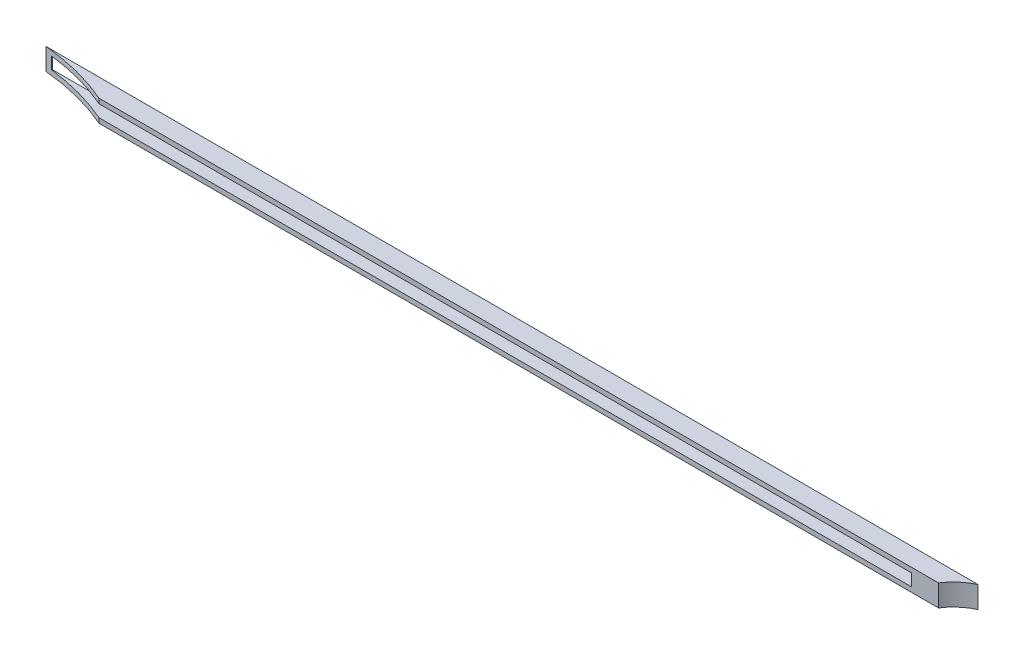
SolidWorks part; units mm, degrees
ref_plane "Front Plane" through (0, 0, 0) normal (0, 0, 1) x (1, 0, 0)
ref_plane "Top Plane" through (0, 0, 0) normal (0, 1, 0) x (1, 0, 0)
ref_plane "Right Plane" through (0, 0, 0) normal (1, 0, 0) x (0, 0, -1)
sketch "Sketch1" plane through (0, 0, 0) normal (0, 0, 1) x (1, 0, 0)
  line L1 (-256.2037, 5.715) -> (256.2037, 5.715)
  line L2 (-256.2037, 5.715) -> (-256.2037, -5.715)
  line L3 (-256.2037, -5.715) -> (256.2037, -5.715)
  line L4 (256.2037, 5.715) -> (256.2037, -5.715)
  line L5 (-256.2037, 5.715) -> (256.2037, -5.715) construction
  line L6 (-256.2037, -5.715) -> (256.2037, 5.715) construction
  line L7 (-230.8037, 3.175) -> (230.8037, 3.175)
  line L8 (-230.8037, 3.175) -> (-230.8037, -3.175)
  line L9 (-230.8037, -3.175) -> (230.8037, -3.175)
  line L10 (230.8037, 3.175) -> (230.8037, -3.175)
  line L11 (-230.8037, 3.175) -> (230.8037, -3.175) construction
  line L12 (-230.8037, -3.175) -> (230.8037, 3.175) construction
  point P0 (0, 0)
  point P6 (0, 0)
  point P11 (-230.8037, 0)
  dimension "D1" = 11.43
  dimension "D2" = 6.35
  dimension "D3" = 512.4074
  dimension "D4" = 25.4
extrude "Boss-Extrude1" add sketch "Sketch1" along normal blind 9.652
sketch "Sketch2" plane through (0, 5.715, 0) normal (0, 1, 0) x (1, 0, 0)
  circle A0 centre (-245.1841, -120.8301) radius 121.3315
  circle A1 centre (267.3382, -24.0848) radius 26.534
  dimension "D1" = 242.663
  dimension "D2" = 53.068
  dimension "D3" = 521.5734
extrude "Cut-Extrude1" cut sketch "Sketch2" against normal through all both and the other way through all
